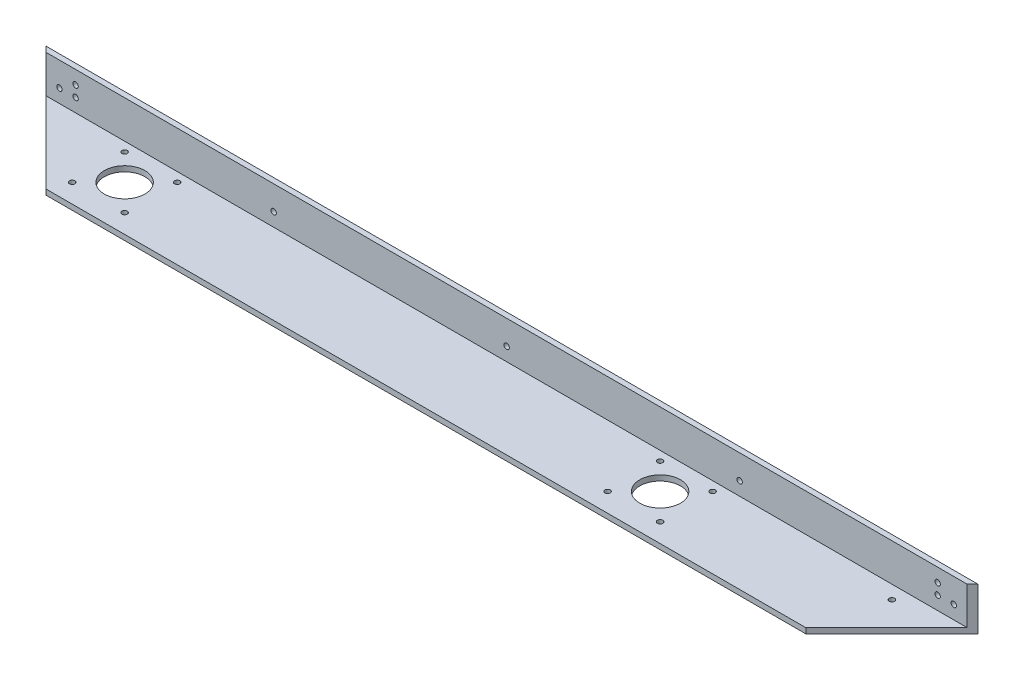
SolidWorks part; units mm, degrees
ref_plane "Front Plane" through (0, 0, 0) normal (0, 0, 1) x (1, 0, 0)
ref_plane "Top Plane" through (0, 0, 0) normal (0, 1, 0) x (1, 0, 0)
ref_plane "Right Plane" through (0, 0, 0) normal (1, 0, 0) x (0, 0, -1)
sketch "Sketch1" plane through (0, 0, 0) normal (1, 0, 0) x (0, 0, -1)
  line L0 (0, 0) -> (-50.8, 0)
  line L1 (-50.8, 0) -> (-50.8, 3.175)
  line L2 (-50.8, 3.175) -> (-3.175, 3.175)
  line L3 (-3.175, 3.175) -> (-3.175, 25.4)
  line L4 (-3.175, 25.4) -> (0, 25.4)
  line L5 (0, 25.4) -> (0, 0)
  dimension "LHeight" = 25.4
  dimension "LWidth" = 50.8
  dimension "LMaterialThickness" = 3.175
  dimension "D1" = 47.625
  dimension "D2" = 22.225
  dimension "D3" = 3.175
extrude "Boss-Extrude1" add sketch "Sketch1" along normal blind 550
chamfer "Chamfer7" distance 50.8 angle 45 1 edges at (0, 1.5875, 50.8)
chamfer "Chamfer8" distance 50.8 angle 45 1 edges at (550, 1.5875, 50.8)
sketch "BotthomHoles-Sketch2" plane through (0, 3.175, 0) normal (0, 1, 0) x (1, 0, 0)
  line L0 (546.825, -3.175) -> (3.175, -3.175) construction
  circle A0 centre (70.575, -24.175) radius 12
  circle A1 centre (386.575, -24.175) radius 12
  circle A2 centre (55.075, -8.675) radius 1.5875
  circle A3 centre (86.075, -8.675) radius 1.5875
  circle A4 centre (371.075, -8.675) radius 1.5875
  circle A5 centre (402.075, -8.675) radius 1.5875
  circle A6 centre (55.075, -39.675) radius 1.5875
  circle A7 centre (86.075, -39.675) radius 1.5875
  circle A8 centre (371.075, -39.675) radius 1.5875
  circle A9 centre (402.075, -39.675) radius 1.5875
  circle A11 centre (510.3125, -11.1125) radius 1.5875
  dimension "D9" = 3.175
  dimension "D10" = 24
  dimension "D2" = 8.675
  dimension "D3" = 31
  dimension "D4" = 15.5
  dimension "D5" = 15.5
  dimension "D6" = 31
  dimension "D7" = 15.5
  dimension "D8" = 31
  dimension "D11" = 21
  dimension "D12" = 316
  dimension "D13" = 70.575
  dimension "D17" = 39.6875
extrude "BottomHoles-Cut-Extrude1" cut sketch "BotthomHoles-Sketch2" against normal through all
sketch "LeftSideHoles-Sketch3" plane through (0, 0, 0) normal (0, 0, -1) x (-1, 0, 0)
  line L0 (0, 0) -> (0, 25.4) construction
  line L1 (-550, 0) -> (-550, 25.4) construction
  line L2 (-550, 25.4) -> (0, 25.4) construction
  circle A1 centre (-529.3625, 17.4625) radius 1.5875
  circle A2 centre (-538.8875, 11.1125) radius 1.5875
  circle A3 centre (-529.3625, 11.1125) radius 1.5875
  circle A4 centre (-11.1125, 11.1125) radius 1.5875
  circle A5 centre (-20.6375, 11.1125) radius 1.5875
  circle A6 centre (-20.6375, 17.4625) radius 1.5875
  circle A8 centre (-412.5, 11.1125) radius 1.5875
  circle A9 centre (-275, 11.1125) radius 1.5875
  circle A10 centre (-137.5, 11.1125) radius 1.5875
  dimension "D7" = 3.175
  dimension "D2" = 20.6375
  dimension "D4" = 11.1125
  dimension "D6" = 20.6375
  dimension "D8" = 137.5
  dimension "D9" = 137.5
  dimension "D10" = 137.5
  dimension "D5" = 11.1125
  dimension "D11" = 11.1125
  dimension "D3" = 7.9375
extrude "LeftSideHoles-Cut-Extrude2" cut sketch "LeftSideHoles-Sketch3" against normal through all
equation "\"LowerRailWidth\"= 2.00in"
equation "\"LowerRailHeight\"= 1.00in"
equation "\"RailThickness\"= .125in'Spec"
equation "\"SideRailHoleY1FromEdge\"= \"HoleOffsetFromEdge\""
equation "\"SideRailHoleX1FromSide\"= \"HoleOffsetFromSide\""
equation "\"StepperHoleDiameter\"= 24mm"
equation "\"StepperMountingHoleDiameter\"= 3.175mm"
equation "\"SideRailLength\"= 550mm"
equation "\"StepperMountingHoleDistance\"= 31mm'Spec"
equation "\"VSWidth\"= 1.25in'Spec"
equation "\"StepperMountingHoleOffsetFromLeftOrRightSide\"= \"StepperMountingHoleOffsetFromItsSide\" + \"RailThickness\""
equation "\"HoleOffsetFromEdge\"= \"RailThickness\" * 2.5"
equation "\"HoleOffsetFromSide\"= \"RailThickness\" * 3.5"
equation "\"StepperMountingHoleOffsetFromItsSide\"= 5.5mm'Spec"
equation "\"SideRailHoleX2FromSide\"= \"VSWidth\" - \"HoleOffsetFromEdge\" - \"RailThickness\"'Equals 20.6375"
equation "\"FasteningHoleDiameter\"= .125in"
equation "\"SideRailHoleY2FromSide\"= \"HoleOffsetFromSide\""
equation "\"LHeight@Sketch1\"=\"LowerRailHeight\""
equation "\"LWidth@Sketch1\"=\"LowerRailWidth\""
equation "\"D1@Chamfer7\"=\"LowerRailWidth\""
equation "\"D1@Chamfer8\"=\"LowerRailWidth\""
equation "\"D2@BotthomHoles-Sketch2\" = \"StepperMountingHoleOffsetFromLeftOrRightSide\""
equation "\"D3@BotthomHoles-Sketch2\" = \"StepperMountingHoleDistance\""
equation "\"D4@BotthomHoles-Sketch2\" = \"StepperMountingHoleDistance\" / 2"
equation "\"D5@BotthomHoles-Sketch2\"= \"StepperMountingHoleDistance\" / 2"
equation "\"D6@BotthomHoles-Sketch2\" = \"StepperMountingHoleDistance\""
equation "\"D7@BotthomHoles-Sketch2\" = \"StepperMountingHoleDistance\" / 2"
equation "\"D8@BotthomHoles-Sketch2\" = \"StepperMountingHoleDistance\""
equation "\"D9@BotthomHoles-Sketch2\" = \"StepperMountingHoleDiameter\""
equation "\"D10@BotthomHoles-Sketch2\" = \"StepperHoleDiameter\""
equation "\"D2@LeftSideHoles-Sketch3\" = \"SideRailHoleX2FromSide\""
equation "\"D4@LeftSideHoles-Sketch3\" = \"SideRailHoleY2FromSide\""
equation "\"D7@LeftSideHoles-Sketch3\" = \"FasteningHoleDiameter\""
equation "\"D1@Boss-Extrude1\"=\"SideRailLength\""
equation "\"D6@LeftSideHoles-Sketch3\"=\"SideRailHoleX2FromSide\""
equation "\"DistanceBetweenFrontToBackStepperHoles\"= \"BedLength\" - \"DistanceFromBedFrontToFirstLeftStepperHole\"'Equals 316"
equation "\"BedOverlap\"= 20mm"
equation "\"BedThirdSize\"= 70mm"
equation "\"BedLWidth\"= \"BedThirdSize\" + \"BedOverlap\"'Equals 90"
equation "\"BedInnerSquareWidth\"= \"BedThirdSize\" * 3'Equals 210"
equation "\"BedInnerSquareLength\"= \"BedInnerSquareWidth\""
equation "\"BedLength\"= \"BedInnerSquareLength\" + \"BedLWidth\" * 2 - \"BedOverlap\" * 2 + \"BedIncreasedByLength\"'Equals 350"
equation "\"D12@BotthomHoles-Sketch2\"=\"DistanceBetweenFrontToBackStepperHoles\""
equation "\"DistanceFromFrontSideToFirstLeftStepperHole\"= \"DistanceFromFrontSideToBedFront\" + \"DistanceFromBedFrontToFirstLeftStepperHole\"'Equals 70.575"
equation "\"D13@BotthomHoles-Sketch2\"=\"DistanceFromFrontSideToFirstLeftStepperHole\""
equation "\"DistanceFromBedFrontToFirstLeftStepperHole\"= \"LeadScrewNutPadSize\" + 10mm'Equals 34"
equation "\"DistanceFromFrontSideToBedFront\"= \"RailThickness\" + \"BeltTensionerDepth\" + 10mm'Equals 36.575"
equation "\"BeltTensionerDepth\"= \"BeltTensionerBackWallThickness\" + \"BeltTensionerInnerDepth\"'Equals 23.4"
equation "\"BeltTensionerBackWallThickness\"= 4mm"
equation "\"20TGT2PulleyDiameter\"= 17.9mm'Spec"
equation "\"BeltTensionerSpaceBetweenPulleyAndWall\"= 1.5mm"
equation "\"BeltTensionerInnerDepth\"= \"20TGT2PulleyDiameter\" + \"BeltTensionerSpaceBetweenPulleyAndWall\""
equation "\"BedIncreasedByLength\"= 0mm"
equation "\"LowerCornerBlockWidth\"= \"LowerRailWidth\" - \"RailThickness\" * 2'Room for left front stepper"
equation "\"D17@BotthomHoles-Sketch2\"=\"CornerEnclosureOffset\""
equation "\"CornerEnclosureOffset\"= \"LowerCornerBlockWidth\" - \"HoleOffsetFromEdge\" + \"RailThickness\""
equation "\"LeadScrewNutMountingHoleFlangeDiameter\"= 22mm'Spec"
equation "\"LeadScrewNutPadSize\"= \"LeadScrewNutMountingHoleFlangeDiameter\" + 2mm'Equals 24"
equation "\"LeftOrRightEnclosureOffsets\"= \"SideRailLength\" / 4"
equation "\"D8@LeftSideHoles-Sketch3\"=\"LeftOrRightEnclosureOffsets\""
equation "\"D9@LeftSideHoles-Sketch3\"=\"LeftOrRightEnclosureOffsets\""
equation "\"D10@LeftSideHoles-Sketch3\"=\"LeftOrRightEnclosureOffsets\""
equation "\"D5@LeftSideHoles-Sketch3\"=\"SideRailHoleX1FromSide\""
equation "\"D11@LeftSideHoles-Sketch3\"=\"SideRailHoleX1FromSide\""
equation "\"D3@LeftSideHoles-Sketch3\"=\"SideRailHoleY1FromEdge\""
